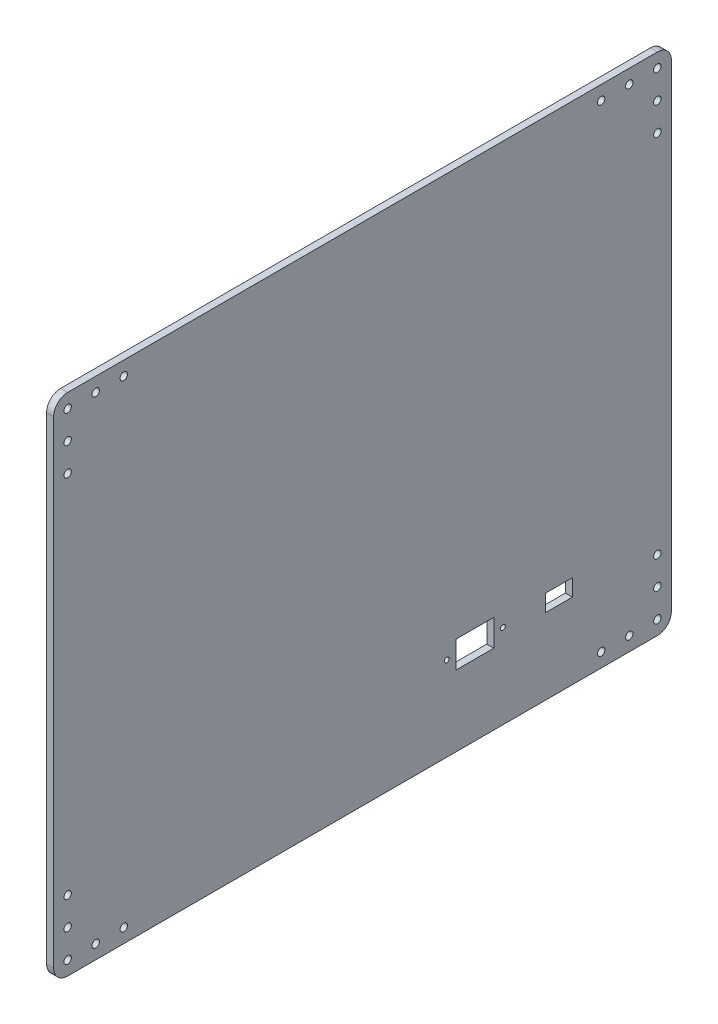
SolidWorks part; units mm, degrees
material "Acrílico (médio-alto impacto)"
ref_plane "Plano frontal" through (0, 0, 0) normal (0, 0, 1) x (1, 0, 0)
ref_plane "Plano superior" through (0, 0, 0) normal (0, 1, 0) x (1, 0, 0)
ref_plane "Plano direito" through (0, 0, 0) normal (1, 0, 0) x (0, 0, -1)
sketch "Esboço1" plane through (0, 0, 0) normal (1, 0, 0) x (0, 0, -1)
  line L1 (-220, 180) -> (220, 180)
  line L2 (-220, 180) -> (-220, -180)
  line L3 (-220, -180) -> (220, -180)
  line L4 (220, 180) -> (220, -180)
  line L5 (-220, 180) -> (220, -180) construction
  line L6 (-220, -180) -> (220, 180) construction
  point P0 (0, 0)
  dimension "D1" = 440
  dimension "D2" = 360
extrude "Ressalto-extrusão1" add sketch "Esboço1" along normal mid plane 5
fillet "Filete1" radius 10 4 edges at (0, 180, -220) (0, -180, -220) (0, -180, 220) (0, 180, 220)
sketch "Esboço2" plane through (2.5, 0, 0) normal (1, 0, 0) x (0, 0, -1)
  line L0 (-220, 170) -> (-220, -170) construction
  line L1 (-210, -180) -> (210, -180) construction
  circle A0 centre (-210, -170) radius 2.65
  circle A1 centre (-190, -170) radius 2.65
  circle A2 centre (-170, -170) radius 2.65
  circle A3 centre (-210, -150) radius 2.65
  circle A4 centre (-210, -130) radius 2.65
  dimension "D1" = 5.3
  dimension "D2" = 10
  dimension "D3" = 10
  dimension "D4" = 3
  dimension "D5" = 3
extrude "Corte-extrusão1" cut sketch "Esboço2" against normal through all
ref_axis "Eixo3" through (-3.3, 0, 0) along (1, 0, 0)
mirror "Espelhar1" about plane through (0, 0, 0) normal (0, 0, 1) of "Corte-extrusão1"
mirror "Espelhar2" about plane through (0, 0, 0) normal (0, 1, 0) of "Espelhar1"
sketch "Esboço3" plane through (2.5, 0, 0) normal (1, 0, 0) x (0, 0, -1)
  line L0 (66.5, -120) -> (93.5, -120) construction
  line L1 (66.5, -129.5) -> (93.5, -129.5)
  line L2 (66.5, -129.5) -> (66.5, -110.5)
  line L3 (66.5, -110.5) -> (93.5, -110.5)
  line L4 (93.5, -129.5) -> (93.5, -110.5)
  line L5 (80, -110.5) -> (80, -129.5) construction
  line L6 (-210, -180) -> (210, -180) construction
  line L7 (130.5, -114) -> (149.5, -114)
  line L8 (130.5, -114) -> (130.5, -126)
  line L9 (130.5, -126) -> (149.5, -126)
  line L10 (149.5, -114) -> (149.5, -126)
  line L11 (130.5, -114) -> (149.5, -126) construction
  line L12 (130.5, -126) -> (149.5, -114) construction
  line L14 (130.5, -120) -> (149.5, -120) construction
  line L15 (220, -170) -> (220, 170) construction
  circle A0 centre (100, -120) radius 1.75
  circle A1 centre (60, -120) radius 1.75
  point P10 (80, -120)
  point P13 (140, -120)
  dimension "D4" = 3.5
  dimension "D1" = 27
  dimension "D2" = 19
  dimension "D3" = 20
  dimension "D5" = 12
  dimension "D6" = 19
  dimension "D7" = 60
  dimension "D8" = 60
  dimension "D9" = 140
extrude "Corte-extrusão2" cut sketch "Esboço3" against normal through all
